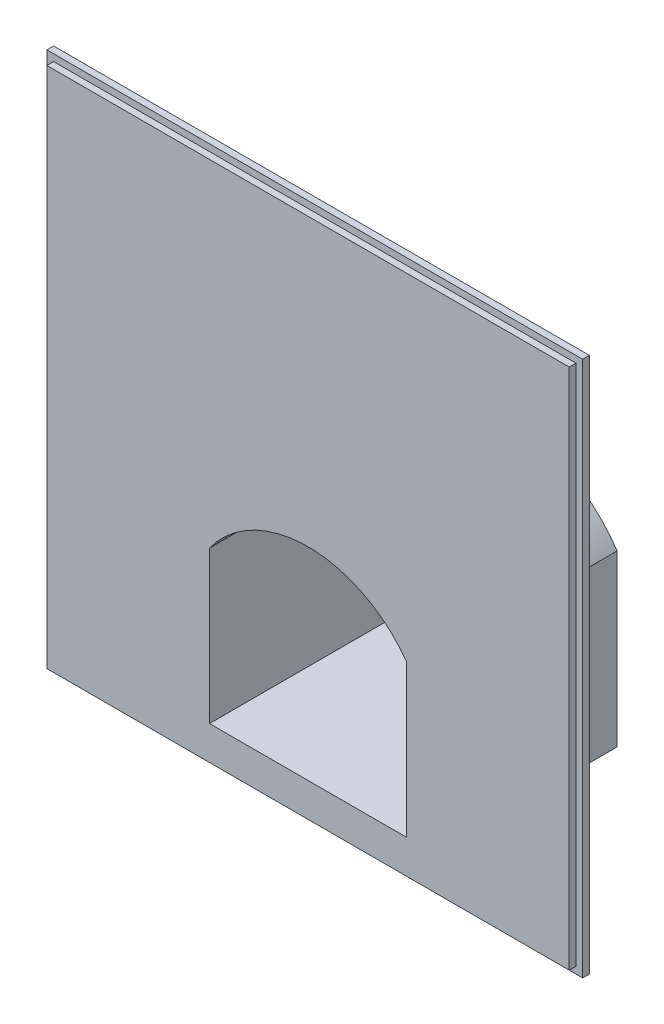
SolidWorks part; units mm, degrees
material "ABS"
ref_plane "Front Plane" through (0, 0, 0) normal (0, 0, 1) x (1, 0, 0)
ref_plane "Top Plane" through (0, 0, 0) normal (0, 1, 0) x (1, 0, 0)
ref_plane "Right Plane" through (0, 0, 0) normal (1, 0, 0) x (0, 0, -1)
ref_axis "Axis X" through (57.4134, 0, 0) along (-1, 0, 0)
ref_axis "Axis Y" through (0, 65.1338, 0) along (0, -1, 0)
ref_axis "Axis Z" through (0, 0, -90.83) along (0, 0, 1)
sketch "Sketch1" plane through (0, 0, 0) normal (0, 0, 1) x (1, 0, 0)
  line L1 (19.85, -19.85) -> (19.85, 19.85)
  line L2 (19.85, 19.85) -> (-19.85, 19.85)
  line L3 (-19.85, 19.85) -> (-19.85, -19.85)
  line L4 (-19.85, -19.85) -> (19.85, -19.85)
  circle A0 centre (0, 0) radius 19.85 construction
  dimension "D1" = 39.7
extrude "Boss-Extrude1" add sketch "Sketch1" along normal blind 1
sketch "Sketch2" plane through (0, 0, 0) normal (0, 0, -1) x (-1, 0, 0)
  line L0 (0, -17.85) -> (0, 17.85) construction
  line L1 (-8.3, -17.85) -> (8.3, -17.85)
  line L2 (-8.3, -17.85) -> (-8.3, -5.2724)
  line L4 (8.3, -17.85) -> (8.3, -5.2724)
  line L5 (19.85, -19.85) -> (-19.85, -19.85) construction
  arc A1 (8.3, -5.2724) -> (-8.3, -5.2724) centre (0, -10.85) ccw
  dimension "D4" = 7
  dimension "D3" = 10
  dimension "D1" = 2
  dimension "D2" = 16.6
extrude "Boss-Extrude2" add sketch "Sketch2" along normal blind 13.6
shell "Shell1" thickness 1 removed face at (0, 0, 1)
sketch "Sketch3" plane through (0, 0, 1) normal (0, 0, 1) x (1, 0, 0)
  line L1 (-19.35, 19.35) -> (19.35, 19.35)
  line L2 (-19.35, 19.35) -> (-19.35, -19.35)
  line L3 (-19.35, -19.35) -> (19.35, -19.35)
  line L4 (-19.85, -19.85) -> (19.85, -19.85)
  line L5 (19.85, -19.85) -> (19.85, 19.85)
  line L6 (19.85, 19.85) -> (-19.85, 19.85)
  line L7 (-19.85, 19.85) -> (-19.85, -19.85)
  line L8 (-19.85, -19.85) -> (19.85, -19.85)
  line L9 (19.85, -19.85) -> (19.85, 19.85)
  line L10 (19.85, 19.85) -> (-19.85, 19.85)
  line L11 (-19.85, 19.85) -> (-19.85, -19.85)
  line L12 (19.35, 19.35) -> (19.35, -19.35)
  dimension "D2" = 0.5
  dimension "D3" = 0.5
  dimension "D4" = 0.5
  dimension "D5" = 0.5
  dimension "D1" = 0
extrude "Cut-Extrude1" cut sketch "Sketch3" against normal blind 0.5
sketch "Sketch4" plane through (0, 0, -13.6) normal (0, 0, -1) x (-1, 0, 0)
  line L0 (0, 0) -> (0, -24.7649) construction
  line L1 (-6.5, -15.55) -> (-4.5, -15.55)
  line L2 (-6.5, -15.55) -> (-6.5, -15.85)
  line L3 (-6.5, -15.85) -> (-4.5, -15.85)
  line L4 (-4.5, -15.55) -> (-4.5, -15.85)
  line L5 (-8.3, -17.85) -> (8.3, -17.85) construction
  line L6 (4.5, -15.55) -> (4.5, -15.85)
  line L7 (6.5, -15.85) -> (4.5, -15.85)
  line L8 (6.5, -15.55) -> (6.5, -15.85)
  line L9 (6.5, -15.55) -> (4.5, -15.55)
  dimension "D1" = 2
  dimension "D2" = 9
  dimension "D3" = 2
  dimension "D4" = 0.3
extrude "Cut-Extrude2" cut sketch "Sketch4" against normal up to next
